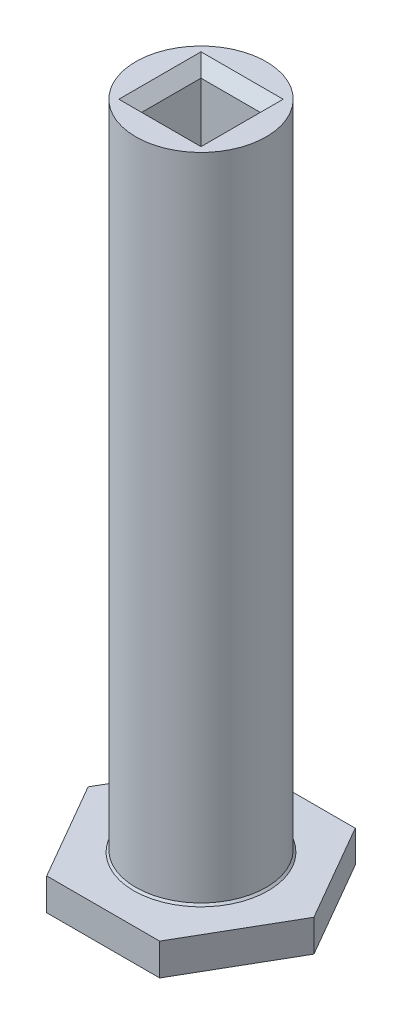
SolidWorks part; units mm, degrees
material "PET"
ref_plane "Front Plane" through (0, 0, 0) normal (0, 0, 1) x (1, 0, 0)
ref_plane "Top Plane" through (0, 0, 0) normal (0, 1, 0) x (1, 0, 0)
ref_plane "Right Plane" through (0, 0, 0) normal (1, 0, 0) x (0, 0, -1)
sketch "Sketch1" plane through (0, 0, 0) normal (0, 1, 0) x (1, 0, 0)
  line L1 (10.9985, -19.05) -> (21.997, 0)
  line L2 (21.997, 0) -> (10.9985, 19.05)
  line L3 (10.9985, 19.05) -> (-10.9985, 19.05)
  line L4 (-10.9985, 19.05) -> (-21.997, 0)
  line L5 (-21.997, 0) -> (-10.9985, -19.05)
  line L6 (-10.9985, -19.05) -> (10.9985, -19.05)
  circle A0 centre (0, 0) radius 19.05 construction
  dimension "D1" = 38.1
extrude "Key" add sketch "Sketch1" along normal blind 6.223
sketch "Sketch2" plane through (0, 6.223, 0) normal (0, 1, 0) x (1, 0, 0)
  circle A0 centre (0, 0) radius 12.7
  dimension "D1" = 25.4
extrude "Shaft and Weight Holder" add sketch "Sketch2" along normal blind 127 separate body
sketch "Sketch3" plane through (0, 133.223, 0) normal (0, 1, 0) x (1, 0, 0)
  line L1 (-5.7785, 5.7785) -> (5.7785, 5.7785)
  line L2 (-5.7785, 5.7785) -> (-5.7785, -5.7785)
  line L3 (-5.7785, -5.7785) -> (5.7785, -5.7785)
  line L4 (5.7785, 5.7785) -> (5.7785, -5.7785)
  line L5 (-5.7785, 5.7785) -> (5.7785, -5.7785) construction
  line L6 (-5.7785, -5.7785) -> (5.7785, 5.7785) construction
  point P0 (0, 0)
  dimension "D1" = 11.557
extrude "8mm Screw Hole" cut sketch "Sketch3" against normal blind 15.875
combine bodies "Combine1" operation type add bodies to combine 103 101
chamfer "Chamfer1" distance 0.381 angle 45 1 edges at (0, 6.223, 12.7)
sketch "Sketch4" plane through (0, 117.348, 0) normal (0, 1, 0) x (1, 0, 0)
  line L0 (-5.7785, 0) -> (5.7785, 0) construction
  line L1 (-5.7785, 5.7785) -> (-5.7785, -5.7785) construction
  line L2 (5.7785, -5.7785) -> (5.7785, 5.7785) construction
  point P6 (0, 0)
chamfer "Chamfer2" distance 2.2225 angle 45 4 edges at (-5.7785, 133.223, 0) (0, 133.223, -5.7785) (5.7785, 133.223, 0) (0, 133.223, 5.7785)
